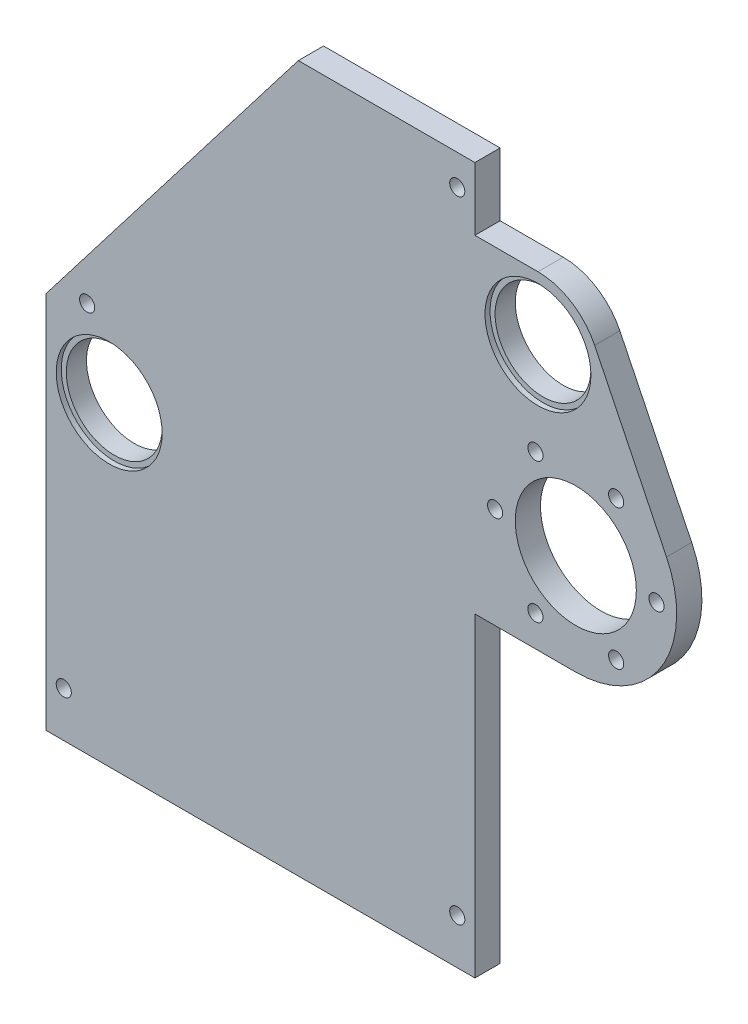
SolidWorks part; units mm, degrees
ref_plane "Front Plane" through (0, 0, 0) normal (0, 0, 1) x (1, 0, 0)
ref_plane "Top Plane" through (0, 0, 0) normal (0, 1, 0) x (1, 0, 0)
ref_plane "Right Plane" through (0, 0, 0) normal (1, 0, 0) x (0, 0, -1)
sketch "Sketch1" plane through (0, 0, 0) normal (0, 0, 1) x (1, 0, 0)
  line L1 (0, 0) -> (50, 0)
  line L2 (0, 0) -> (0, 50) construction
  line L3 (0, 50) -> (50, 50) construction
  line L4 (50, 0) -> (50, 50) construction
  line L5 (0, 0) -> (50, 50) construction
  line L6 (0, 50) -> (50, 0) construction
  line L11 (0, 0) -> (-25, 0)
  line L12 (-25, 0) -> (-25, 75)
  line L13 (-25, 75) -> (50, 75)
  line L14 (0, 50) -> (-25, 75) construction
  line L15 (50, 75) -> (50, 140)
  line L16 (-11.0566, 65) -> (-13.9434, 65) construction
  line L17 (-13.9434, 65) -> (-15.3868, 62.5) construction
  line L18 (-15.3868, 62.5) -> (-13.9434, 60) construction
  line L19 (-13.9434, 60) -> (-11.0566, 60) construction
  line L20 (-11.0566, 60) -> (-9.6132, 62.5) construction
  line L21 (-9.6132, 62.5) -> (-11.0566, 65) construction
  line L22 (53, 140) -> (53, 0) construction
  line L23 (-25, 75) -> (25, 140)
  line L24 (50, 140) -> (60, 140)
  line L25 (60, 140) -> (60, 0)
  line L26 (60, 0) -> (50, 0)
  line L27 (25, 140) -> (50, 140)
  line L28 (72.5, 127.5) -> (60, 127.5)
  line L29 (72.5, 102.5) -> (60, 102.5)
  line L30 (80, 102.5) -> (60, 102.5)
  line L31 (80, 62.5) -> (60, 62.5)
  line L32 (97.9775, 91.264) -> (83.736, 120.4775)
  circle A1 centre (-12.5, 62.5) radius 9.5
  circle A2 centre (-12.5, 62.5) radius 2.5 construction
  circle A3 centre (-12.5, 62.5) radius 5 construction
  circle A4 centre (56.5, 134) radius 1.5
  circle A5 centre (56.5, 9) radius 1.5
  circle A6 centre (-12.5, 62.5) radius 10.5
  circle A7 centre (-21.5, 9) radius 1.5
  circle A8 centre (72.5, 115) radius 9.5
  circle A9 centre (72.5, 115) radius 12.5
  circle A10 centre (72.5, 115) radius 10.5
  circle A11 centre (80, 82.5) radius 12
  circle A13 centre (80, 82.5) radius 20
  circle A14 centre (64, 82.5) radius 1.5
  circle A15 centre (72, 96.3564) radius 1.5
  circle A16 centre (88, 96.3564) radius 1.5
  circle A17 centre (96, 82.5) radius 1.5
  circle A18 centre (88, 68.6436) radius 1.5
  circle A19 centre (72, 68.6436) radius 1.5
  circle A20 centre (-16.8672, 77.372) radius 1.5
  circle A21 centre (-16.8672, 77.372) radius 5
  point P4 (25, 25)
  point P6 (25, 25)
  point P63 (80, 82.5)
  point P65 (0, 0)
  dimension "D5" = 19
  dimension "D7" = 10
  dimension "D10" = 3
  dimension "D16" = 3
  dimension "D18" = 21
  dimension "D19" = 3
  dimension "D22" = 19
  dimension "D23" = 25
  dimension "D25" = 21
  dimension "D26" = 24
  dimension "D27" = 3
  dimension "D29" = 40
  dimension "D31" = 3
  dimension "D32" = 10
  dimension "D1" = 50
  dimension "D2" = 50
  dimension "D3" = 75
  dimension "D4" = 75
  dimension "D6" = 5
  dimension "D8" = 65
  dimension "D9" = 10
  dimension "D11" = 3
  dimension "D12" = 3.5
  dimension "D13" = 6
  dimension "D14" = 3.5
  dimension "D15" = 9
  dimension "D17" = 25
  dimension "D20" = 9
  dimension "D21" = 3.5
  dimension "D24" = 25
  dimension "D28" = 16
  dimension "D30" = 6
extrude "Boss-Extrude1" add sketch "Sketch1" along normal blind 5 contours L13 L12 L11 L1 L4 A1 | L26 L25 L24 L15 L4 | L13 L15 | A9 L28 L25 | A9 A10 | A9 L25 L29 | A13 A11 | A13 L32 A9 L30 | A13 L30 L29 L25 | A13 L25 L31 | A21 L23 L13 | L13 A21 | A21 L13 A20 region at (22.7788, 42.9152, 0) region at (-22.7787, 76.4212, 0) region at (64.4674, 66.9674, 0) region at (-21.7271, 77.7651, 0) region at (-16.8672, 73.9208, 0) region at (23.7957, 102.6053, 0) region at (64.4674, 98.0326, 0) region at (66.2579, 96.2421, 0) region at (62.7921, 105.2921, 0) region at (86.7757, 105.3373, 0) region at (62.7921, 124.7079, 0) region at (63.9112, 123.5888, 0)
extrude "Boss-Extrude2" add sketch "Sketch1<3>" along normal blind 4 contours A6 A1 | A10 A8 region at (-6.3857, 70.668, 0) region at (62.297, 115, 0)
sketch "Sketch1<3>" plane through (0, 0, 0) normal (0, 0, 1) x (1, 0, 0) same geometry as "Sketch1"
